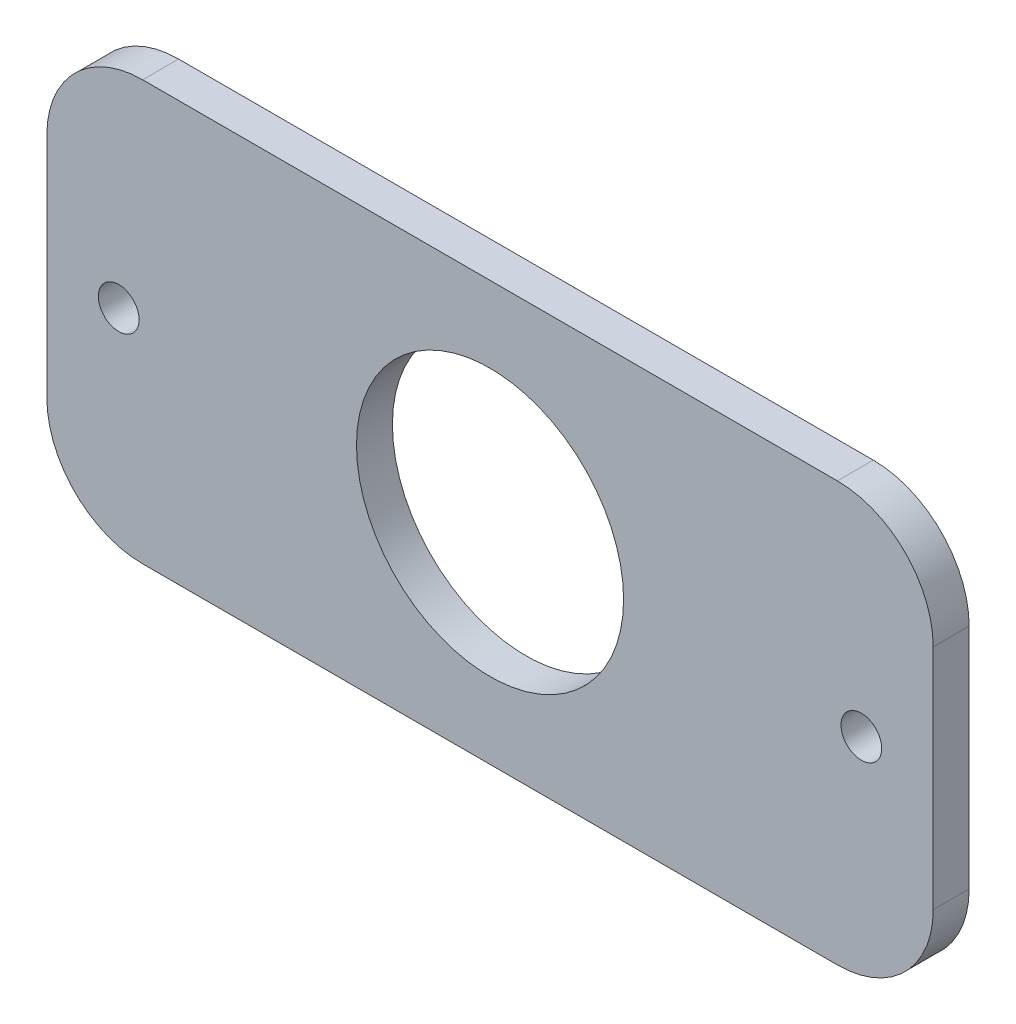
SolidWorks part; units mm, degrees
ref_plane "Plan de face" through (0, 0, 0) normal (0, 0, 1) x (1, 0, 0)
ref_plane "Plan de dessus" through (0, 0, 0) normal (0, 1, 0) x (1, 0, 0)
ref_plane "Plan de droite" through (0, 0, 0) normal (1, 0, 0) x (0, 0, -1)
sketch "Esquisse1" plane through (0, 0, 0) normal (0, 0, 1) x (1, 0, 0)
  line L1 (0, 0) -> (74, 0)
  line L2 (0, 0) -> (0, 35)
  line L3 (0, 35) -> (74, 35)
  line L4 (74, 0) -> (74, 35)
  circle A0 centre (37, 17.5) radius 11.15
  circle A1 centre (6, 17.5) radius 1.5
  circle A2 centre (68, 17.5) radius 1.5
  dimension "D1" = 22.3
  dimension "D8" = 3
  dimension "D11" = 3
  dimension "D2" = 35
  dimension "D3" = 17.5
  dimension "D4" = 74
  dimension "D5" = 37
  dimension "D6" = 17.5
  dimension "D7" = 17.5
  dimension "D9" = 6
  dimension "D10" = 6
extrude "Boss.-Extru.1" add sketch "Esquisse1" along normal blind 3
hole_wizard "Dégagement M31" positions "Esquisse4" profile "Esquisse5" hole size "M3" standard "ISO" end condition up to next
sketch "Esquisse4" plane through (0, 0, 3) normal (0, 0, 1) x (1, 0, 0)
  point P0 (6, 17.5)
  point P3 (68, 17.5)
sketch "Esquisse5" plane through (6, 17.5, 3) normal (1, 0, 0) x (0, -1, 0)
  line L0 (0, 0) -> (0, 3)
  line L1 (0, 3) -> (1.7, 3)
  line L2 (1.7, 3) -> (1.7, 0)
  line L5 (1.7, 0) -> (0, 0)
  line L11 (0, -6.35) -> (0, 107.95) construction
  dimension "Diamètre du perçage jusqu'au prochain" = 3.4
  dimension "Profondeur du perçage jusqu'au prochain" = 3
fillet "Congé1" radius 8 4 edges at (0, 35, 1.5) (74, 35, 1.5) (74, 0, 1.5) (0, 0, 1.5)
equation "\"D3@Esquisse1\"=\"D2@Esquisse1\"/2"
equation "\"D5@Esquisse1\"=\"D4@Esquisse1\"/2"
equation "\"D6@Esquisse1\"=\"D2@Esquisse1\"/2"
equation "\"D7@Esquisse1\"=\"D2@Esquisse1\"/2"
